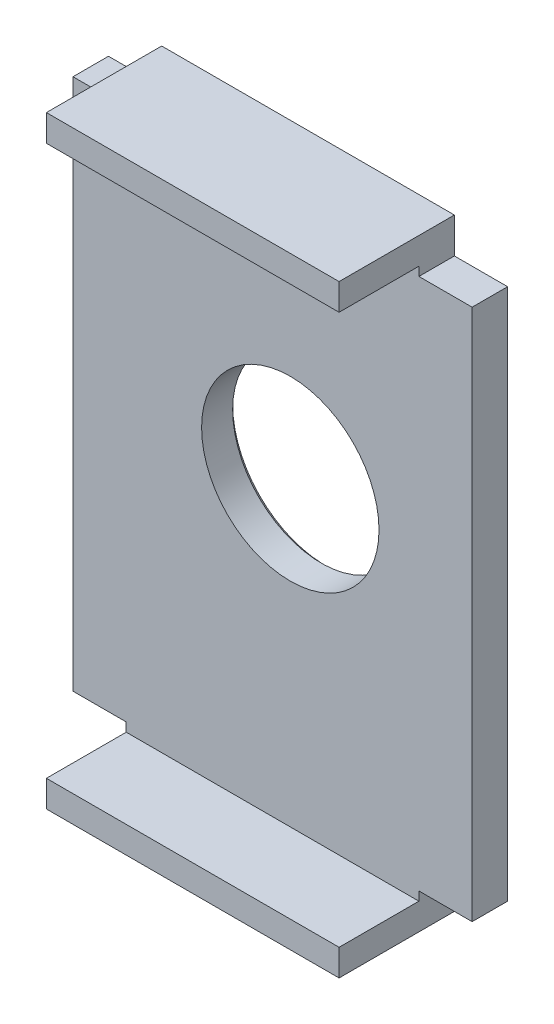
SolidWorks part; units mm, degrees
ref_plane "Front Plane" through (0, 0, 0) normal (0, 0, 1) x (1, 0, 0)
ref_plane "Top Plane" through (0, 0, 0) normal (0, 1, 0) x (1, 0, 0)
ref_plane "Right Plane" through (0, 0, 0) normal (1, 0, 0) x (0, 0, -1)
sketch "Sketch1" plane through (0, 0, 0) normal (0, 0, 1) x (1, 0, 0)
  line L5 (-22.5, -30) -> (22.5, -30)
  line L6 (-22.5, -30) -> (-22.5, 30)
  line L7 (-22.5, 30) -> (22.5, 30)
  line L8 (22.5, -30) -> (22.5, 30)
  line L9 (-22.5, -30) -> (22.5, 30) construction
  line L10 (-22.5, 30) -> (22.5, -30) construction
  circle A2 centre (2, 3) radius 10
  point P0 (0, 0)
  point P5 (2, -3)
  point P8 (2.16, -2.88)
  point P9 (2, 5.0277)
  dimension "D3" = 20
  dimension "D4" = 20.5
  dimension "D1" = 60
  dimension "D2" = 45
  dimension "D5" = 3
extrude "Boss-Extrude1" add sketch "Sketch1" along normal mid plane 4
sketch "Sketch3" plane through (0, 0, -2) normal (0, 0, -1) x (-1, 0, 0)
  line L0 (-22.5, 30) -> (22.5, 30) construction
  line L1 (-16.5, 30) -> (16.5, 30)
  line L2 (-16.5, 30) -> (-16.5, 34)
  line L3 (-16.5, 34) -> (16.5, 34)
  line L4 (16.5, 30) -> (16.5, 34)
  line L5 (-22.5, -30) -> (-22.5, 30) construction
  line L6 (22.5, 30) -> (22.5, -30) construction
  line L7 (22.5, -30) -> (-22.5, -30) construction
  line L8 (-16.5, -30) -> (16.5, -30)
  line L9 (-16.5, -30) -> (-16.5, -34)
  line L10 (-16.5, -34) -> (16.5, -34)
  line L11 (16.5, -30) -> (16.5, -34)
  dimension "D1" = 6
  dimension "D2" = 6
  dimension "D3" = 4
extrude "Boss-Extrude3" add sketch "Sketch3" against normal blind 13
chamfer "Chamfer1" distance 0.5 angle 45 1 edges at (12, 3, -2)
sketch "Sketch4" plane through (0, 0, 11) normal (0, 0, 1) x (1, 0, 0)
  line L0 (16.5, 34) -> (16.5, 30) construction
  line L1 (-16.5, 30) -> (16.5, 30)
  line L2 (-16.5, 30) -> (-16.5, 31)
  line L3 (-16.5, 31) -> (16.5, 31)
  line L4 (16.5, 30) -> (16.5, 31)
  line L5 (-16.5, -34) -> (-16.5, -30) construction
  line L6 (16.5, -30) -> (-16.5, -30)
  line L7 (16.5, -30) -> (16.5, -31)
  line L8 (16.5, -31) -> (-16.5, -31)
  line L9 (-16.5, -30) -> (-16.5, -31)
  dimension "D1" = 1
extrude "Cut-Extrude1" cut sketch "Sketch4" against normal up to vertex (9 mm away) up to point (16.5, -30, 2)
equation "\"padding\"=6"
equation "\"wall_thick_ness\"=4"
equation "\"D1@Sketch3\"=\"padding\""
equation "\"D2@Sketch3\"=\"padding\""
equation "\"D3@Sketch3\"=\"wall_thick_ness\""
equation "\"D1@Boss-Extrude1\"=\"wall_thick_ness\""
